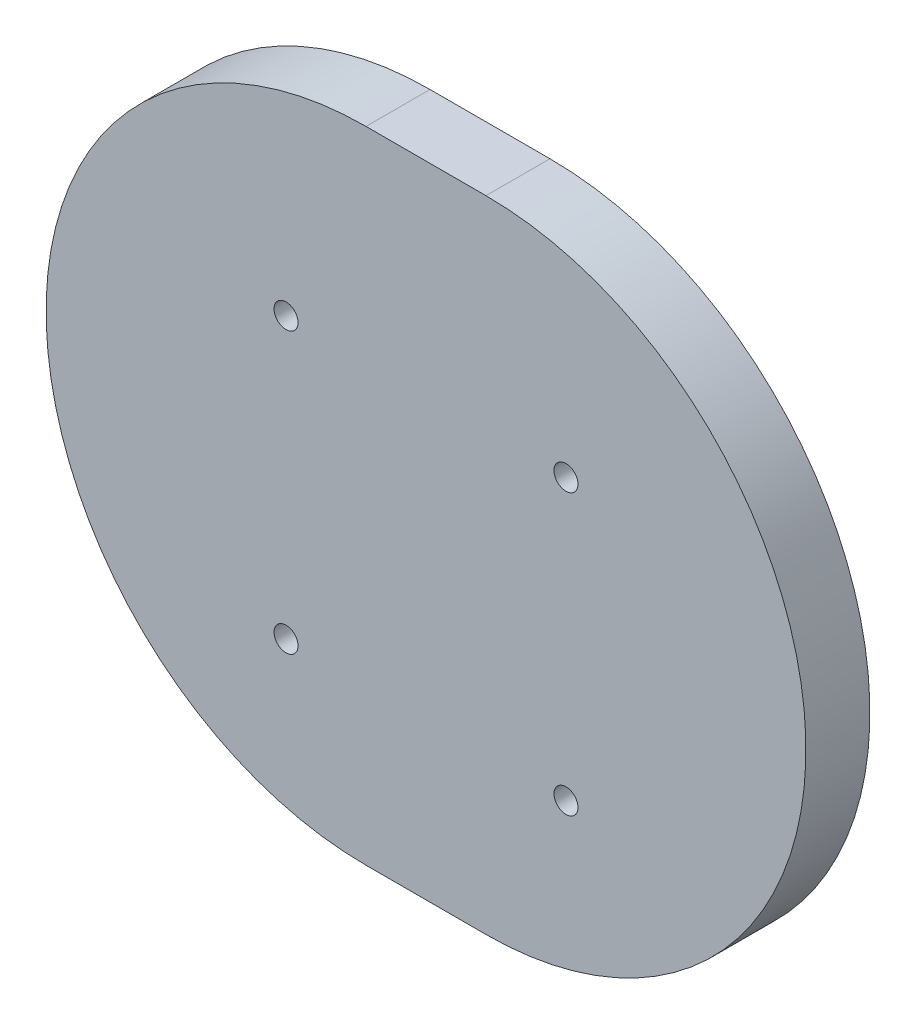
SolidWorks part; units mm, degrees
ref_plane "Front Plane" through (0, 0, 0) normal (0, 0, 1) x (1, 0, 0)
ref_plane "Top Plane" through (0, 0, 0) normal (0, 1, 0) x (1, 0, 0)
ref_plane "Right Plane" through (0, 0, 0) normal (1, 0, 0) x (0, 0, -1)
sketch "Sketch1" plane through (0, 0, 0) normal (0, 0, 1) x (1, 0, 0)
  line L0 (-1.5, 0) -> (1.5, 0) construction
  line L1 (-1.5, 8) -> (1.5, 8)
  line L2 (-1.5, -8) -> (1.5, -8)
  line L4 (3.5, -4.1) -> (-3.5, -4.1) construction
  line L5 (3.5, -4.1) -> (3.5, 2.9) construction
  line L6 (3.5, 2.9) -> (-3.5, 2.9) construction
  line L7 (-3.5, -4.1) -> (-3.5, 2.9) construction
  arc A0 (-1.5, 8) -> (-1.5, -8) centre (-1.5, 0) ccw
  arc A1 (1.5, -8) -> (1.5, 8) centre (1.5, 0) ccw
  circle A2 centre (3.5, 2.9) radius 0.3
  circle A3 centre (-3.5, 2.9) radius 0.3
  circle A4 centre (-3.5, -4.1) radius 0.3
  circle A5 centre (3.5, -4.1) radius 0.3
  point P3 (0, 0)
  point P12 (3.5, -0.6)
  point P13 (0, 2.9)
  point P14 (0, 8)
  dimension "D1" = 8
  dimension "D6" = 0.6
  dimension "D7" = 0.6
  dimension "D8" = 0.6
  dimension "D9" = 0.6
  dimension "D2" = 3
  dimension "D3" = 8.6
  dimension "D4" = 7
  dimension "D5" = 7
extrude "Boss-Extrude1" add sketch "Sketch1" along normal blind 1.6
